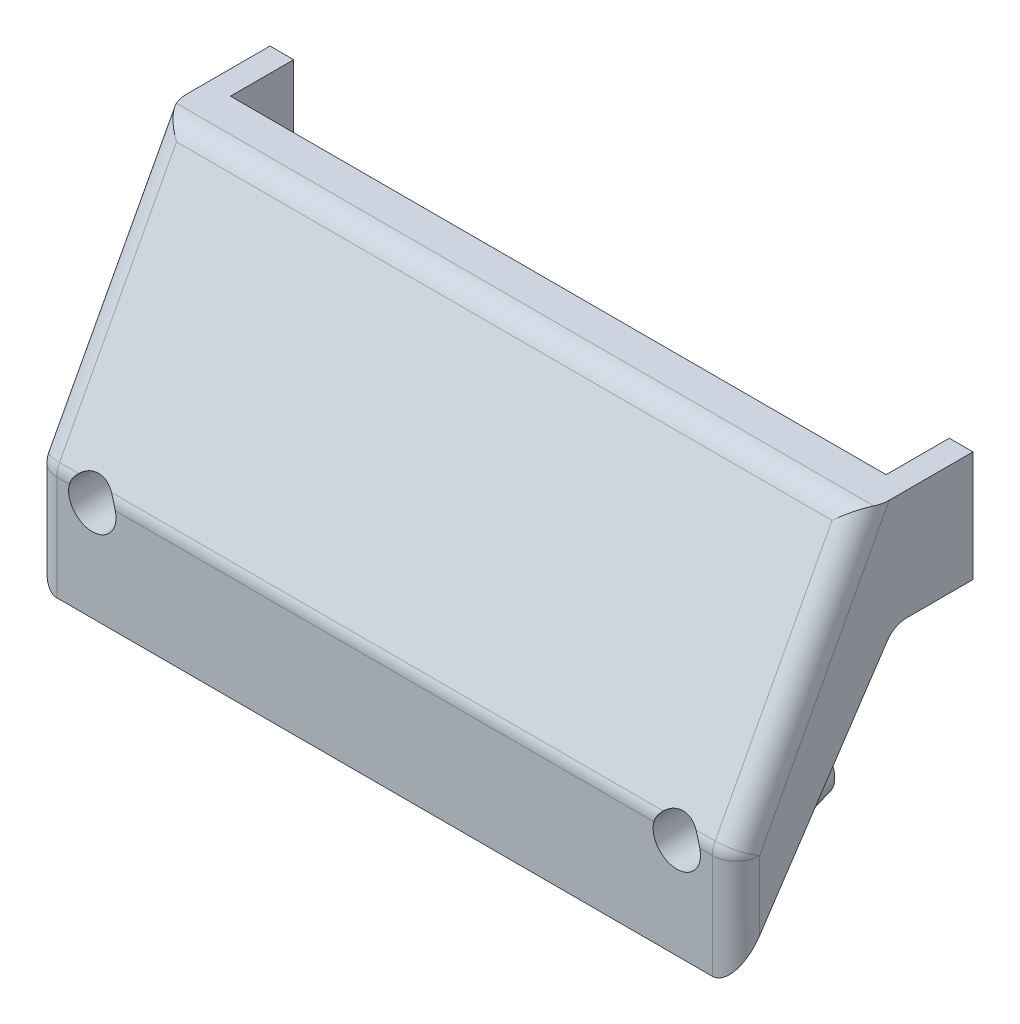
SolidWorks part; units mm, degrees
material "ABS"
ref_plane "Plano frontal" through (0, 0, 0) normal (0, 0, 1) x (1, 0, 0)
ref_plane "Plano superior" through (0, 0, 0) normal (0, 1, 0) x (1, 0, 0)
ref_plane "Plano direito" through (0, 0, 0) normal (1, 0, 0) x (0, 0, -1)
sketch "Esboço1" plane through (0, 0, 0) normal (0, 0, 1) x (1, 0, 0)
  line L1 (-44.5, 4) -> (44.5, 4)
  line L2 (-44.5, 4) -> (-44.5, -40)
  line L3 (-44.5, -40) -> (44.5, -40)
  line L4 (44.5, 4) -> (44.5, -40)
  dimension "D1" = 44.5
  dimension "D2" = 44.5
  dimension "D3" = 40
  dimension "D4" = 4
extrude "Ressalto-extrusão1" add sketch "Esboço1" along normal blind 30
sketch "Esboço2" plane through (44.5, 0, 0) normal (1, 0, 0) x (0, 0, -1)
  line L0 (-30, -40) -> (-10, -10)
  line L2 (0, -10) -> (0, -40)
  line L3 (0, -40) -> (-30, -40)
  line L4 (-10, -10) -> (0, -10)
  dimension "D1" = 10
  dimension "D2" = 30
extrude "Corte-extrusão1" cut sketch "Esboço2" against normal through all
chamfer "Chanfro2" distance 16 distance2 30 1 edges at (0, 4, 30) first distance on face at (0, 4, 15)
fillet "Filete1" radius 3 6 edges at (-44.5, -33, 30) (44.5, -33, 30) (0, 4, 14) (0, -26, 30) (-44.5, -11, 22) (44.5, -11, 22)
shell "Casca2" thickness 3 removed face at (0, -28.8107, 22.5404) removed face at (0, -3, 0)
sketch "Esboço3" plane through (0, 4, 0) normal (0, 1, 0) x (1, 0, 0)
  line L5 (44.5, 0) -> (-44.5, 0) construction
  line L6 (-41.5, 0) -> (41.5, 0)
  line L7 (-41.5, 0) -> (-41.5, -8)
  line L8 (-41.5, -8) -> (41.5, -8)
  line L9 (41.5, 0) -> (41.5, -8)
  line L10 (-44.5, -10.6) -> (-44.5, 0) construction
  line L11 (44.5, -10.6) -> (44.5, 0) construction
  dimension "D1" = 3
  dimension "D2" = 3
  dimension "D3" = 8
extrude "Corte-extrusão2" cut sketch "Esboço3" against normal through all
fillet "Filete2" radius 3 2 edges at (-43, -10, 10) (43, -10, 10)
fillet "Filete3" radius 3 2 edges at (41.5, -12.875, 19.6) (-41.5, -12.875, 19.6)
sketch "Esboço4" plane through (0, 0, 30) normal (0, 0, 1) x (1, 0, 0)
  line L0 (-41.5, -40) -> (41.5, -40) construction
  line L1 (0, 4) -> (0, -40) construction
  line L2 (-44.1471, 4) -> (44.1471, 4) construction
  circle A0 centre (-37, -27.5) radius 1.75
  circle A1 centre (37, -27.5) radius 1.75
  dimension "D1" = 12.5
  dimension "D2" = 37
  dimension "D3" = 3.5
extrude "Corte-extrusão3" cut sketch "Esboço4" against normal through all
sketch "Esboço5" plane through (0, 0, 27) normal (0, 0, -1) x (-1, 0, 0)
  line L5 (0, 4) -> (0, -40) construction
  line L6 (41.5, 4) -> (-41.5, 4) construction
  line L7 (41.5, -40) -> (-41.5, -40) construction
  circle A4 centre (-37, -27.5) radius 1.75
  circle A5 centre (-37, -27.5) radius 4
  circle A6 centre (37, -27.5) radius 4
  circle A7 centre (37, -27.5) radius 1.75
  dimension "D1" = 8
extrude "Ressalto-extrusão2" add sketch "Esboço5" along normal blind 10
sketch "Esboço6" plane through (0, 0, 17) normal (0, 0, -1) x (-1, 0, 0)
  line L0 (0, 4) -> (0, -40) construction
  line L1 (41.5, 4) -> (-41.5, 4) construction
  line L2 (41.5, -40) -> (-41.5, -40) construction
  circle A0 centre (-37, -27.5) radius 1.75
  circle A1 centre (-37, -27.5) radius 3
  circle A2 centre (37, -27.5) radius 3
  circle A3 centre (37, -27.5) radius 1.75
  dimension "D1" = 6
extrude "Ressalto-extrusão3" add sketch "Esboço6" along normal blind 4
sketch "Esboço7" plane through (0, 0, 30) normal (0, 0, 1) x (1, 0, 0)
  line L0 (0, -40) -> (0, 4) construction
  line L1 (-41.5, -40) -> (41.5, -40) construction
  line L2 (-44.1471, 4) -> (44.1471, 4) construction
  circle A0 centre (-37, -27.5) radius 3
  circle A1 centre (37, -27.5) radius 3
  dimension "D1" = 6
extrude "Corte-extrusão4" cut sketch "Esboço7" against normal offset from surface (11 mm away) 2 up to face at (33, -27.5, 17)
chamfer "Chanfro3" distance 1 distance2 4 1 edges at (-34, -27.5, 17) first distance on face at (-34, -27.5, 17)
chamfer "Chanfro4" distance 1 distance2 4 1 edges at (34, -27.5, 17) first distance on face at (33, -27.5, 17)
sketch "Esboço8" plane through (0, 0, 8) normal (0, 0, -1) x (-1, 0, 0)
  line L1 (-41.5, -7) -> (41.5, -7)
  line L2 (-41.5, -7) -> (-41.5, -10)
  line L3 (-41.5, -10) -> (41.5, -10)
  line L4 (41.5, -7) -> (41.5, -10)
extrude "Corte-extrusão5" cut sketch "Esboço8" against normal blind 2
